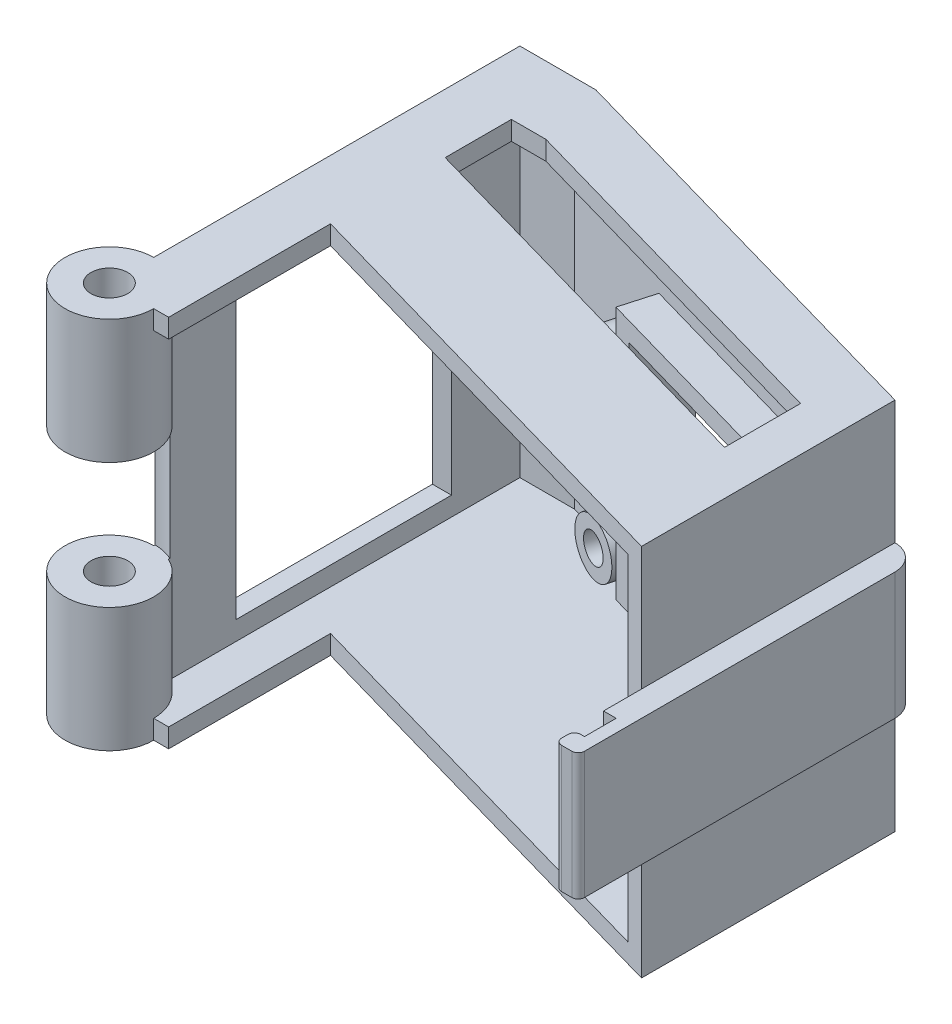
SolidWorks part; units mm, degrees
ref_plane "Frontal Plane" through (0, 0, 0) normal (0, 0, 1) x (1, 0, 0)
ref_plane "Horizontal Plane" through (0, 0, 0) normal (0, 1, 0) x (1, 0, 0)
ref_plane "Profile Plane" through (0, 0, 0) normal (1, 0, 0) x (0, 0, -1)
sketch "Sketch2" plane through (0, 0, 0) normal (0, 1, 0) x (1, 0, 0)
  line L1 (18.0725, -16.3423) -> (18.0725, 6.6577)
  line L2 (18.0725, 6.6577) -> (-14.9275, 16.058)
  line L3 (-14.9275, 16.058) -> (-20.9275, 16.058)
  line L4 (-20.9275, 16.058) -> (-20.9275, -16.3423)
  line L6 (-20.9275, -16.3423) -> (18.0725, -16.3423)
  dimension "D1" = 15.9
  dimension "D3" = 23
  dimension "D4" = 6
  dimension "D5" = 39
extrude "Boss-Extrude1" add sketch "Sketch2" along normal blind 29.5
shell "Shell1" thickness 1.5 removed face at (-1.4275, 14.75, 16.3423)
sketch "Sketch11" plane through (2.6996, 0, -9.4771) normal (-0.274, 0, 0.9617) x (0.9617, 0, 0.274)
  line L0 (14.4247, 1.5) -> (-18.5462, 1.5) construction
  line L1 (7.1747, 2.25) -> (-8.8253, 2.25)
  line L2 (7.1747, 2.25) -> (7.1747, 22.25)
  line L3 (7.1747, 22.25) -> (-8.8253, 22.25)
  line L4 (-8.8253, 2.25) -> (-8.8253, 22.25)
  line L5 (14.4247, 28) -> (14.4247, 1.5) construction
  dimension "D1" = 0.75
  dimension "D2" = 7.25
  dimension "D3" = 20
  dimension "D4" = 16
extrude "Boss-Extrude6" add sketch "Sketch11" along normal blind 2.75
sketch "Sketch3" plane through (2.6996, 0, -9.4771) normal (-0.274, 0, 0.9617) x (0.9617, 0, 0.274)
  line L0 (5.6747, 3.75) -> (5.6747, 20.75)
  line L1 (5.6747, 20.75) -> (-7.3253, 20.75)
  line L2 (-7.3253, 20.75) -> (-7.3253, 3.75)
  line L3 (-7.3253, 3.75) -> (5.6747, 3.75)
  line L4 (14.4247, 28) -> (14.4247, 1.5) construction
  line L8 (15.5571, 0) -> (-18.7557, 0) construction
  dimension "D1" = 3.75
  dimension "D2" = 8.75
  dimension "D3" = 13
  dimension "D4" = 17
extrude "Cut-Extrude1" cut sketch "Sketch3" against normal through all both and the other way through all
sketch "Sketch4" plane through (2.6996, 0, -9.4771) normal (-0.274, 0, 0.9617) x (0.9617, 0, 0.274)
  line L0 (5.6747, 3.75) -> (5.6747, 20.75) construction
  line L2 (-0.8253, 20.75) -> (-0.8253, 3.75) construction
  line L3 (5.6747, 20.75) -> (-7.3253, 20.75) construction
  line L4 (-7.3253, 3.75) -> (5.6747, 3.75) construction
  line L5 (14.4247, 1.5) -> (-18.5462, 1.5) construction
  line L6 (5.6747, 3.75) -> (5.6747, 20.75) construction
  circle A0 centre (9.6747, 4.25) radius 2.125
  circle A1 centre (9.6747, 16.75) radius 2.125
  circle A2 centre (-11.3253, 16.75) radius 2.125
  circle A3 centre (-11.3253, 4.25) radius 2.125
  dimension "D4" = 4.25
  dimension "D1" = 4
  dimension "D2" = 12.5
  dimension "D3" = 2.75
  dimension "D5" = 4
extrude "Boss-Extrude2" add sketch "Sketch4" along normal blind 2.8
sketch "Sketch5" plane through (1.9325, 0, -6.7843) normal (-0.274, 0, 0.9617) x (0.9617, 0, 0.274)
  circle A0 centre (9.6747, 4.25) radius 1.125
  circle A1 centre (9.6747, 16.75) radius 1.125
  circle A2 centre (-11.3253, 4.25) radius 1.125
  circle A3 centre (-11.3253, 16.75) radius 1.125
  dimension "D1" = 2.25
extrude "Cut-Extrude2" cut sketch "Sketch5" against normal through all
sketch "Sketch6" plane through (0, 29.5, 0) normal (0, 1, 0) x (1, 0, 0)
  circle A0 centre (-20.9275, -16.3423) radius 3.5
  dimension "D1" = 7
extrude "Boss-Extrude3" add sketch "Sketch6" against normal blind 9.8
sketch "Sketch7" plane through (0, 0, 0) normal (0, -1, 0) x (-1, 0, 0)
  circle A0 centre (20.9275, -16.3423) radius 3.5
  dimension "D1" = 7
extrude "Boss-Extrude4" add sketch "Sketch7" against normal blind 9.8
sketch "Sketch8" plane through (0, 19.7, 0) normal (0, -1, 0) x (-1, 0, 0)
  circle A0 centre (20.9275, -16.3423) radius 3.6
  dimension "D1" = 7.2
extrude "Cut-Extrude3" cut sketch "Sketch8" along normal up to surface (9.9 mm away) up to face at (-20.5572, 9.8, 16.3631)
sketch "Sketch9" plane through (0, 0, 0) normal (0, -1, 0) x (-1, 0, 0)
  circle A0 centre (20.9275, -16.3423) radius 1.45
  dimension "D1" = 2.9
extrude "Cut-Extrude4" cut sketch "Sketch9" against normal through all
sketch "Sketch10" plane through (2.6996, 0, -9.4771) normal (-0.274, 0, 0.9617) x (0.9617, 0, 0.274)
  line L0 (-7.3253, 3.75) -> (5.6747, 3.75) construction
  line L1 (7.1747, 2.25) -> (-8.8253, 2.25)
  line L2 (7.1747, 2.25) -> (7.1747, 22.25)
  line L3 (7.1747, 22.25) -> (-8.8253, 22.25)
  line L4 (-8.8253, 2.25) -> (-8.8253, 22.25)
  line L5 (5.6747, 20.75) -> (-7.3253, 20.75) construction
  line L6 (5.6747, 3.75) -> (5.6747, 20.75) construction
  line L7 (-7.3253, 20.75) -> (-7.3253, 3.75) construction
  point P12 (-7.3253, 12.25)
  dimension "D1" = 1.5
  dimension "D2" = 1.5
  dimension "D3" = 1.5
  dimension "D4" = 1.5
sketch "Sketch12" plane through (18.0725, 0, 0) normal (1, 0, 0) x (0, 0, -1)
  line L0 (-16.3423, 29.5) -> (-16.3423, 0) construction
  line L1 (-16.3423, 9.75) -> (6.6577, 9.75)
  line L2 (-16.3423, 9.75) -> (-16.3423, 19.75)
  line L3 (-16.3423, 19.75) -> (6.6577, 19.75)
  line L4 (6.6577, 9.75) -> (6.6577, 19.75)
  line L5 (6.6577, 29.5) -> (6.6577, 0) construction
  point P6 (6.6577, 14.75)
  point P9 (6.6577, 14.75)
  dimension "D1" = 10
extrude "Boss-Extrude7" add sketch "Sketch12" along normal blind 1
sketch "Sketch13" plane through (19.0725, 0, 0) normal (1, 0, 0) x (0, 0, -1)
  line L0 (-16.3423, 19.75) -> (-16.3423, 9.75) construction
  line L1 (6.6577, 9.75) -> (-20.3423, 9.75)
  line L2 (6.6577, 9.75) -> (6.6577, 19.75)
  line L3 (6.6577, 19.75) -> (-20.3423, 19.75)
  line L4 (-20.3423, 9.75) -> (-20.3423, 19.75)
  dimension "D1" = 4
extrude "Boss-Extrude8" add sketch "Sketch13" along normal blind 1
sketch "Sketch14" plane through (19.0725, 0, 0) normal (-1, 0, 0) x (0, 0, 1)
  line L0 (16.3423, 19.75) -> (20.3423, 19.75) construction
  line L1 (20.3423, 9.75) -> (18.8423, 9.75)
  line L2 (20.3423, 9.75) -> (20.3423, 19.75)
  line L3 (20.3423, 19.75) -> (18.8423, 19.75)
  line L4 (18.8423, 9.75) -> (18.8423, 19.75)
  dimension "D1" = 1.5
extrude "Boss-Extrude9" add sketch "Sketch14" along normal blind 0.8
fillet "Fillet2" radius 0.5 2 edges at (20.0725, 14.75, 20.3423) (18.2725, 14.75, 18.8423)
fillet "Fillet3" radius 0.5 1 edges at (18.2725, 14.75, 20.3423)
fillet "Fillet4" radius 2 1 edges at (20.0725, 14.75, -6.6577)
sketch "Sketch15" plane through (0, 29.5, 0) normal (0, 1, 0) x (1, 0, 0)
  line L0 (18.0725, -13.3423) -> (-16.2475, -3.566)
  line L1 (-16.2475, -3.566) -> (-16.2475, -6.4782)
  line L2 (-16.2475, -6.4782) -> (-16.2475, -16.3423)
  line L4 (18.0725, 6.6577) -> (-14.9275, 16.058) construction
  line L6 (-17.4275, -16.3423) -> (18.0725, -16.3423) construction
  line L7 (-16.2475, -16.3423) -> (18.0725, -16.3423)
  line L8 (18.0725, -16.3423) -> (18.0725, -13.3423)
  dimension "D1" = 34.32
  dimension "D2" = 3
extrude "Cut-Extrude5" cut sketch "Sketch15" against normal through all
sketch "Sketch16" plane through (-20.9275, 0, 0) normal (-1, 0, 0) x (0, 0, 1)
  line L0 (-16.058, 0) -> (12.8423, 0) construction
  line L1 (7.8423, 3) -> (-9.1577, 3)
  line L2 (7.8423, 3) -> (7.8423, 26.5)
  line L3 (7.8423, 26.5) -> (-9.1577, 26.5)
  line L4 (-9.1577, 3) -> (-9.1577, 26.5)
  line L5 (-16.058, 29.5) -> (12.8423, 29.5) construction
  line L6 (12.8423, 19.7) -> (12.8423, 29.5) construction
  dimension "D1" = 3
  dimension "D2" = 3
  dimension "D3" = 5
  dimension "D4" = 17
extrude "Cut-Extrude6" cut sketch "Sketch16" against normal up to next
sketch "Sketch17" plane through (0, 29.5, 0) normal (0, 1, 0) x (1, 0, 0)
  line L0 (-16.2475, 5.483) -> (14.5791, -3.2982)
  line L1 (14.5791, -3.2982) -> (14.5791, 2.7018)
  line L2 (14.5791, 2.7018) -> (-13.5214, 10.7065)
  line L3 (-13.5214, 10.7065) -> (-16.2475, 10.7065)
  line L4 (-16.2475, 10.7065) -> (-16.2475, 5.483)
  line L5 (18.0725, -13.3423) -> (-16.2475, -3.566) construction
  line L7 (18.0725, 6.6577) -> (-14.9275, 16.058) construction
  dimension "D1" = 4.7616
  dimension "D2" = 6
extrude "Cut-Extrude7" cut sketch "Sketch17" against normal up to surface (1.5 mm away) up to face at (-8.789, 28, 3.4268)
